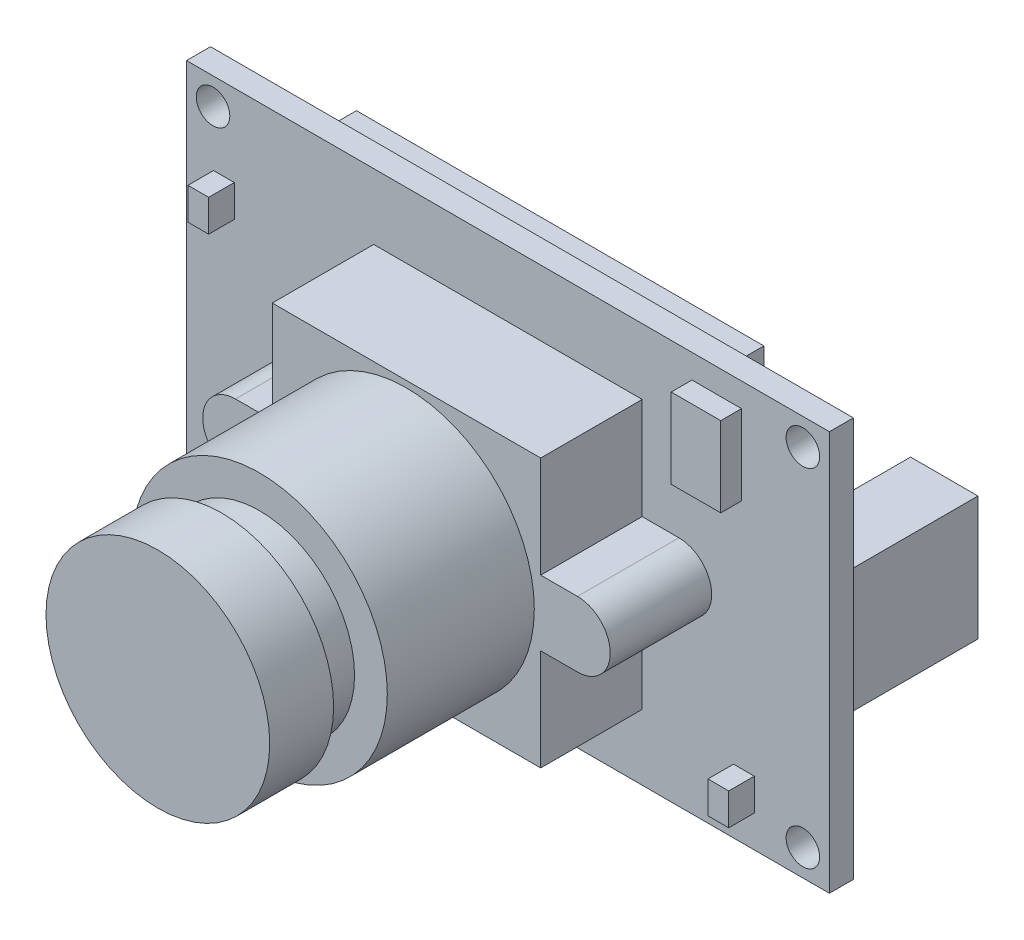
SolidWorks part; units mm, degrees
ref_plane "Front Plane" through (0, 0, 0) normal (0, 0, 1) x (1, 0, 0)
ref_plane "Top Plane" through (0, 0, 0) normal (0, 1, 0) x (1, 0, 0)
ref_plane "Right Plane" through (0, 0, 0) normal (1, 0, 0) x (0, 0, -1)
sketch "Sketch2" plane through (0, 0, 0) normal (0, 0, 1) x (1, 0, 0)
  line L0 (0, 0) -> (0, 6.003) construction
  line L1 (20.1168, 12.5095) -> (-20.1168, 12.5095)
  line L2 (20.1168, 12.5095) -> (20.1168, -12.5095)
  line L3 (20.1168, -12.5095) -> (-20.1168, -12.5095)
  line L4 (-20.1168, 12.5095) -> (-20.1168, -12.5095)
  line L5 (20.1168, 12.5095) -> (-20.1168, -12.5095) construction
  line L6 (20.1168, -12.5095) -> (-20.1168, 12.5095) construction
  line L7 (-1000, 0) -> (49000, 0) construction
  circle A0 centre (-18.4568, 10.8495) radius 1.05
  circle A1 centre (-18.4568, -10.8495) radius 1.05
  circle A2 centre (18.4568, -10.8495) radius 1.05
  circle A3 centre (18.4568, 10.8495) radius 1.05
  point P0 (0, 0)
  dimension "D5" = 2.1
  dimension "D1" = 40.2336
  dimension "D2" = 25.019
  dimension "D3" = 1.66
  dimension "D4" = 1.66
extrude "Boss-Extrude1" add sketch "Sketch2" along normal blind 1.5
sketch "Sketch3" plane through (0, 0, 1.5) normal (0, 0, 1) x (1, 0, 0)
  line L0 (-8.4, -2.05) -> (-8.4, -8.4)
  line L1 (8.4, 8.4) -> (-8.4, 8.4)
  line L2 (8.4, 8.4) -> (8.4, 2.05)
  line L3 (8.4, -8.4) -> (-8.4, -8.4)
  line L4 (-8.4, 8.4) -> (-8.4, 2.05)
  line L5 (8.4, 8.4) -> (-8.4, -8.4) construction
  line L6 (8.4, -8.4) -> (-8.4, 8.4) construction
  line L7 (-10.7, 2.05) -> (-8.4, 2.05)
  line L8 (0, -1000) -> (0, 49000) construction
  line L9 (-10.7, -2.05) -> (-8.4, -2.05)
  line L10 (10.7, 2.05) -> (8.4, 2.05)
  line L11 (10.7, -2.05) -> (8.4, -2.05)
  line L12 (8.4, -2.05) -> (8.4, -8.4)
  line L13 (-1000, 0) -> (49000, 0) construction
  arc A0 (-10.7, 2.05) -> (-10.7, -2.05) centre (-10.7, 0) ccw
  arc A1 (10.7, 2.05) -> (10.7, -2.05) centre (10.7, 0) cw
  point P0 (0, 0)
  dimension "D1" = 16.8
  dimension "D2" = 16.8
  dimension "D3" = 4.1
  dimension "D4" = 2.3
extrude "Boss-Extrude2" add sketch "Sketch3" along normal blind 6.35
sketch "Sketch4" plane through (0, 0, 7.85) normal (0, 0, 1) x (1, 0, 0)
  circle A0 centre (0, 0) radius 8
  dimension "D1" = 16
extrude "Boss-Extrude3" add sketch "Sketch4" along normal blind 9.2
sketch "Sketch5" plane through (0, 0, 17.05) normal (0, 0, 1) x (1, 0, 0)
  circle A0 centre (0, 0) radius 5.95
  dimension "D1" = 11.9
extrude "Boss-Extrude4" add sketch "Sketch5" along normal blind 2.36
sketch "Sketch6" plane through (0, 0, 19.41) normal (0, 0, 1) x (1, 0, 0)
  circle A0 centre (0, 0) radius 7
extrude "Boss-Extrude5" add sketch "Sketch6" along normal blind 4
sketch "Sketch7" plane through (0, 0, 0) normal (0, 0, -1) x (-1, 0, 0)
  line L0 (0, 0) -> (-20.1168, 0) construction
  line L1 (-15.3968, -3.875) -> (-19.6168, -3.875)
  line L2 (-15.3968, -3.875) -> (-15.3968, 3.875)
  line L3 (-15.3968, 3.875) -> (-19.6168, 3.875)
  line L4 (-19.6168, -3.875) -> (-19.6168, 3.875)
  line L5 (-20.1168, -12.5095) -> (-20.1168, 12.5095) construction
  point P9 (-19.6168, 0)
  dimension "D1" = 7.75
  dimension "D2" = 4.22
  dimension "D3" = 0.5
extrude "Boss-Extrude6" add sketch "Sketch7" along normal blind 8.3
sketch "Sketch8" plane through (0, 0, 0) normal (0, 0, -1) x (-1, 0, 0)
  line L0 (20.1168, 12.5095) -> (20.1168, -12.5095) construction
  line L1 (15.6768, -10.8695) -> (6.6768, -10.8695)
  line L2 (15.6768, -10.8695) -> (15.6768, -7.9395)
  line L3 (15.6768, -7.9395) -> (6.6768, -7.9395)
  line L4 (6.6768, -10.8695) -> (6.6768, -7.9395)
  line L5 (20.1168, -12.5095) -> (-20.1168, -12.5095) construction
  dimension "D1" = 4.44
  dimension "D2" = 1.64
  dimension "D3" = 9
  dimension "D4" = 2.93
extrude "Boss-Extrude7" add sketch "Sketch8" along normal blind 4.35
sketch "Sketch9" plane through (0, 0, 1.5) normal (0, 0, 1) x (1, 0, 0)
  line L0 (20.1168, -12.5095) -> (20.1168, 12.5095) construction
  line L1 (11.5168, 11.0095) -> (14.6168, 11.0095)
  line L2 (11.5168, 11.0095) -> (11.5168, 6.0095)
  line L3 (11.5168, 6.0095) -> (14.6168, 6.0095)
  line L4 (14.6168, 11.0095) -> (14.6168, 6.0095)
  line L5 (20.1168, 12.5095) -> (-20.1168, 12.5095) construction
  dimension "D1" = 3.1
  dimension "D2" = 5
  dimension "D3" = 5.5
  dimension "D4" = 1.5
extrude "Boss-Extrude8" add sketch "Sketch9" along normal blind 1.3
sketch "Sketch10" plane through (0, 0, 0) normal (0, 0, -1) x (-1, 0, 0)
  line L0 (-20.1168, -12.5095) -> (-20.1168, 12.5095) construction
  line L1 (-13.1168, 12.2095) -> (12.3832, 12.2095)
  line L2 (-13.1168, 12.2095) -> (-13.1168, 4.2095)
  line L3 (-13.1168, 4.2095) -> (12.3832, 4.2095)
  line L4 (12.3832, 12.2095) -> (12.3832, 4.2095)
  line L5 (-13.1168, 12.2095) -> (12.3832, 4.2095) construction
  line L6 (-13.1168, 4.2095) -> (12.3832, 12.2095) construction
  line L7 (-20.1168, 12.5095) -> (20.1168, 12.5095) construction
  point P0 (-0.3668, 8.2095)
  dimension "D1" = 25.5
  dimension "D2" = 8
  dimension "D3" = 7
  dimension "D4" = 0.3
extrude "Boss-Extrude9" add sketch "Sketch10" along normal blind 1.4
sketch "Sketch11" plane through (0, 0, 1.5) normal (0, 0, 1) x (1, 0, 0)
  line L0 (20.1168, -12.5095) -> (20.1168, 12.5095) construction
  line L1 (15.4168, -10.5095) -> (14.1168, -10.5095)
  line L2 (15.4168, -10.5095) -> (15.4168, -8.5095)
  line L3 (15.4168, -8.5095) -> (14.1168, -8.5095)
  line L4 (14.1168, -10.5095) -> (14.1168, -8.5095)
  line L5 (-20.1168, -12.5095) -> (20.1168, -12.5095) construction
  line L6 (-17.1271, 5.3916) -> (-18.4271, 5.3916)
  line L7 (-17.1271, 5.3916) -> (-17.1271, 7.3916)
  line L8 (-17.1271, 7.3916) -> (-18.4271, 7.3916)
  line L9 (-18.4271, 5.3916) -> (-18.4271, 7.3916)
  dimension "D1" = 1.3
  dimension "D2" = 2
  dimension "D3" = 6
  dimension "D4" = 2
extrude "Boss-Extrude10" add sketch "Sketch11" along normal blind 1.6
sketch "Sketch12" plane through (0, 0, 0) normal (0, 0, -1) x (-1, 0, 0)
  line L0 (-20.1168, 12.5095) -> (20.1168, 12.5095) construction
  line L1 (19.1168, 5.1095) -> (16.1168, 5.1095)
  line L2 (19.1168, 5.1095) -> (19.1168, 8.1095)
  line L3 (19.1168, 8.1095) -> (16.1168, 8.1095)
  line L4 (16.1168, 5.1095) -> (16.1168, 8.1095)
  line L5 (20.1168, 12.5095) -> (20.1168, -12.5095) construction
  dimension "D1" = 3
  dimension "D2" = 3
  dimension "D3" = 7.4
  dimension "D4" = 1
extrude "Boss-Extrude11" add sketch "Sketch12" along normal blind 1.4
sketch "Sketch13" plane through (0, 0, 0) normal (0, 0, -1) x (-1, 0, 0)
  line L0 (-20.1168, -12.5095) -> (-20.1168, 12.5095) construction
  line L1 (-14.1478, -9.3853) -> (-10.9728, -9.3853)
  line L2 (-14.1478, -9.3853) -> (-14.1478, -12.0015)
  line L3 (-14.1478, -12.0015) -> (-10.9728, -12.0015)
  line L4 (-10.9728, -9.3853) -> (-10.9728, -12.0015)
  line L5 (20.1168, -12.5095) -> (-20.1168, -12.5095) construction
  line L7 (-7.1628, -7.1755) -> (1.3462, -7.1755)
  line L8 (-7.1628, -7.1755) -> (-7.1628, -12.0015)
  line L9 (-7.1628, -12.0015) -> (1.3462, -12.0015)
  line L10 (1.3462, -7.1755) -> (1.3462, -12.0015)
  dimension "D1" = 3.175
  dimension "D2" = 2.6162
  dimension "D3" = 5.969
  dimension "D4" = 0.508
  dimension "D5" = 8.509
  dimension "D6" = 4.826
  dimension "D7" = 12.954
  dimension "D8" = 0.508
extrude "Boss-Extrude12" add sketch "Sketch13" along normal blind 2.7432
